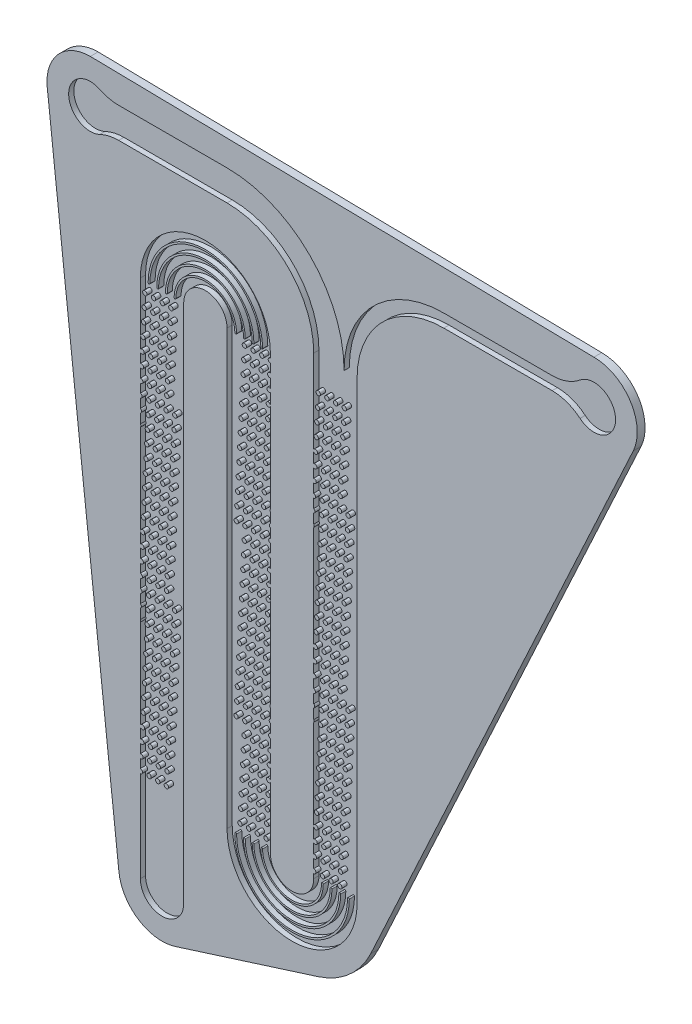
SolidWorks part; units mm, degrees
ref_plane "Front Plane" through (0, 0, 0) normal (0, 0, 1) x (1, 0, 0)
ref_plane "Top Plane" through (0, 0, 0) normal (0, 1, 0) x (1, 0, 0)
ref_plane "Right Plane" through (0, 0, 0) normal (1, 0, 0) x (0, 0, -1)
sketch "Model" plane through (0, 0, 0) normal (0, 0, 1) x (1, 0, 0)
  line L0 (0, 0) -> (0, 1)
  line L1 (0, 2) -> (0, 4.0254)
  line L2 (0, 4.9746) -> (0, 7.1113)
  line L3 (0, 7.8887) -> (0, 10.3341)
  line L4 (0, 10.6659) -> (0, 31.2411)
  line L5 (0, 31.7589) -> (0, 34.0795)
  line L6 (0, 34.9205) -> (0, 37.013)
  line L7 (0, 37.987) -> (0, 40.0019)
  line L8 (0, 40.9981) -> (0, 43.0422)
  line L9 (0, 43.9578) -> (0, 46.1513)
  line L10 (0, 46.8487) -> (0, 70.1796)
  line L11 (0, 70.8204) -> (0, 73.0543)
  line L12 (0, 73.9457) -> (0, 76.0048)
  line L13 (0, 76.9952) -> (0, 79.0078)
  line L14 (0, 79.9922) -> (0, 82.0642)
  line L15 (0, 82.9358) -> (0, 85.203)
  line L16 (0, 85.797) -> (0, 100)
  line L17 (10, 0) -> (10, 100)
  line L18 (30, 100) -> (30, 99)
  line L19 (30, 98) -> (30, 95.9746)
  line L20 (30, 95.0254) -> (30, 92.8887)
  line L21 (30, 92.1113) -> (30, 89.6659)
  line L22 (30, 89.3341) -> (30, 68.7589)
  line L23 (30, 68.2411) -> (30, 65.9205)
  line L24 (30, 65.0795) -> (30, 62.987)
  line L25 (30, 62.013) -> (30, 59.9981)
  line L26 (30, 59.0019) -> (30, 56.9578)
  line L27 (30, 56.0422) -> (30, 53.8487)
  line L28 (30, 53.1513) -> (30, 29.8204)
  line L29 (30, 29.1796) -> (30, 26.9457)
  line L30 (30, 26.0543) -> (30, 23.9952)
  line L31 (30, 23.0048) -> (30, 20.9922)
  line L32 (30, 20.0078) -> (30, 17.9358)
  line L33 (30, 17.0642) -> (30, 14.797)
  line L34 (30, 14.203) -> (30, 0)
  line L35 (20, 100) -> (20, 0)
  line L36 (40, 0) -> (40, 1)
  line L37 (40, 2) -> (40, 4.0254)
  line L38 (40, 4.9746) -> (40, 7.1113)
  line L39 (40, 7.8887) -> (40, 10.3341)
  line L40 (40, 10.6659) -> (40, 31.2411)
  line L41 (40, 31.7589) -> (40, 34.0795)
  line L42 (40, 34.9205) -> (40, 37.013)
  line L43 (40, 37.987) -> (40, 40.0019)
  line L44 (40, 40.9981) -> (40, 43.0422)
  line L45 (40, 43.9578) -> (40, 46.1513)
  line L46 (40, 46.8487) -> (40, 70.1796)
  line L47 (40, 70.8204) -> (40, 73.0543)
  line L48 (40, 73.9457) -> (40, 76.0048)
  line L49 (40, 76.9952) -> (40, 79.0078)
  line L50 (40, 79.9922) -> (40, 82.0642)
  line L51 (40, 82.9358) -> (40, 85.203)
  line L52 (40, 85.797) -> (40, 100)
  line L53 (50, 0) -> (50, 100)
  line L54 (0, 0) -> (0, -20)
  line L55 (10, 0) -> (10, -20)
  line L56 (75, 125) -> (95, 125)
  line L57 (75, 128) -> (95, 128)
  line L58 (75, 125) -> (70, 125)
  line L59 (75, 128) -> (70, 128)
  line L60 (15, 125) -> (-5, 125)
  line L61 (15, 132) -> (-5, 132)
  line L62 (15, 125) -> (20, 125)
  line L63 (15, 132) -> (20, 132)
  line L64 (40, 100) -> (40, 105)
  line L65 (50, 100) -> (50, 105)
  arc A0 (0, 1) -> (0, 2) centre (0, 1.5) ccw
  circle A1 centre (2, 1.5) radius 0.5
  circle A2 centre (4, 1.5) radius 0.5
  circle A3 centre (6, 1.5) radius 0.5
  arc A4 (0, 4.0254) -> (0, 4.9746) centre (0.1572, 4.5) ccw
  circle A5 centre (2.1572, 4.5) radius 0.5
  circle A6 centre (4.1572, 4.5) radius 0.5
  circle A7 centre (6.1572, 4.5) radius 0.5
  arc A8 (0, 7.1113) -> (0, 7.8887) centre (0.3144, 7.5) ccw
  circle A9 centre (2.3144, 7.5) radius 0.5
  circle A10 centre (4.3144, 7.5) radius 0.5
  circle A11 centre (6.3144, 7.5) radius 0.5
  arc A12 (0, 10.3341) -> (0, 10.6659) centre (0.4717, 10.5) ccw
  circle A13 centre (2.4717, 10.5) radius 0.5
  circle A14 centre (4.4717, 10.5) radius 0.5
  circle A15 centre (6.4717, 10.5) radius 0.5
  circle A16 centre (0.6289, 13.5) radius 0.5
  circle A17 centre (2.6289, 13.5) radius 0.5
  circle A18 centre (4.6289, 13.5) radius 0.5
  circle A19 centre (6.6289, 13.5) radius 0.5
  circle A20 centre (0.7861, 16.5) radius 0.5
  circle A21 centre (2.7861, 16.5) radius 0.5
  circle A22 centre (4.7861, 16.5) radius 0.5
  circle A23 centre (6.7861, 16.5) radius 0.5
  circle A24 centre (0.9433, 19.5) radius 0.5
  circle A25 centre (2.9433, 19.5) radius 0.5
  circle A26 centre (4.9433, 19.5) radius 0.5
  circle A27 centre (6.9433, 19.5) radius 0.5
  circle A28 centre (1.1006, 22.5) radius 0.5
  circle A29 centre (3.1006, 22.5) radius 0.5
  circle A30 centre (5.1006, 22.5) radius 0.5
  circle A31 centre (7.1006, 22.5) radius 0.5
  circle A32 centre (1.2578, 25.5) radius 0.5
  circle A33 centre (3.2578, 25.5) radius 0.5
  circle A34 centre (5.2578, 25.5) radius 0.5
  circle A35 centre (7.2578, 25.5) radius 0.5
  circle A36 centre (1.415, 28.5) radius 0.5
  circle A37 centre (3.415, 28.5) radius 0.5
  circle A38 centre (5.415, 28.5) radius 0.5
  circle A39 centre (7.415, 28.5) radius 0.5
  arc A40 (0, 31.2411) -> (0, 31.7589) centre (-0.4278, 31.5) ccw
  circle A41 centre (1.5722, 31.5) radius 0.5
  circle A42 centre (3.5722, 31.5) radius 0.5
  circle A43 centre (5.5722, 31.5) radius 0.5
  circle A44 centre (7.5722, 31.5) radius 0.5
  arc A45 (0, 34.0795) -> (0, 34.9205) centre (-0.2705, 34.5) ccw
  circle A46 centre (1.7295, 34.5) radius 0.5
  circle A47 centre (3.7295, 34.5) radius 0.5
  circle A48 centre (5.7295, 34.5) radius 0.5
  circle A49 centre (7.7295, 34.5) radius 0.5
  arc A50 (0, 37.013) -> (0, 37.987) centre (-0.1133, 37.5) ccw
  circle A51 centre (1.8867, 37.5) radius 0.5
  circle A52 centre (3.8867, 37.5) radius 0.5
  circle A53 centre (5.8867, 37.5) radius 0.5
  circle A54 centre (7.8867, 37.5) radius 0.5
  arc A55 (0, 40.0019) -> (0, 40.9981) centre (0, 40.5) ccw
  circle A56 centre (2.0439, 40.5) radius 0.5
  circle A57 centre (4.0439, 40.5) radius 0.5
  circle A58 centre (6.0439, 40.5) radius 0.5
  arc A59 (0, 43.0422) -> (0, 43.9578) centre (0.2011, 43.5) ccw
  circle A60 centre (2.2011, 43.5) radius 0.5
  circle A61 centre (4.2011, 43.5) radius 0.5
  circle A62 centre (6.2011, 43.5) radius 0.5
  arc A63 (0, 46.1513) -> (0, 46.8487) centre (0.3584, 46.5) ccw
  circle A64 centre (2.3584, 46.5) radius 0.5
  circle A65 centre (4.3584, 46.5) radius 0.5
  circle A66 centre (6.3584, 46.5) radius 0.5
  circle A67 centre (0.5156, 49.5) radius 0.5
  circle A68 centre (2.5156, 49.5) radius 0.5
  circle A69 centre (4.5156, 49.5) radius 0.5
  circle A70 centre (6.5156, 49.5) radius 0.5
  circle A71 centre (0.6728, 52.5) radius 0.5
  circle A72 centre (2.6728, 52.5) radius 0.5
  circle A73 centre (4.6728, 52.5) radius 0.5
  circle A74 centre (6.6728, 52.5) radius 0.5
  circle A75 centre (0.83, 55.5) radius 0.5
  circle A76 centre (2.83, 55.5) radius 0.5
  circle A77 centre (4.83, 55.5) radius 0.5
  circle A78 centre (6.83, 55.5) radius 0.5
  circle A79 centre (0.9872, 58.5) radius 0.5
  circle A80 centre (2.9872, 58.5) radius 0.5
  circle A81 centre (4.9872, 58.5) radius 0.5
  circle A82 centre (6.9872, 58.5) radius 0.5
  circle A83 centre (1.1445, 61.5) radius 0.5
  circle A84 centre (3.1445, 61.5) radius 0.5
  circle A85 centre (5.1445, 61.5) radius 0.5
  circle A86 centre (7.1445, 61.5) radius 0.5
  circle A87 centre (1.3017, 64.5) radius 0.5
  circle A88 centre (3.3017, 64.5) radius 0.5
  circle A89 centre (5.3017, 64.5) radius 0.5
  circle A90 centre (7.3017, 64.5) radius 0.5
  circle A91 centre (1.4589, 67.5) radius 0.5
  circle A92 centre (3.4589, 67.5) radius 0.5
  circle A93 centre (5.4589, 67.5) radius 0.5
  circle A94 centre (7.4589, 67.5) radius 0.5
  arc A95 (0, 70.1796) -> (0, 70.8204) centre (-0.3839, 70.5) ccw
  circle A96 centre (1.6161, 70.5) radius 0.5
  circle A97 centre (3.6161, 70.5) radius 0.5
  circle A98 centre (5.6161, 70.5) radius 0.5
  circle A99 centre (7.6161, 70.5) radius 0.5
  arc A100 (0, 73.0543) -> (0, 73.9457) centre (-0.2266, 73.5) ccw
  circle A101 centre (1.7734, 73.5) radius 0.5
  circle A102 centre (3.7734, 73.5) radius 0.5
  circle A103 centre (5.7734, 73.5) radius 0.5
  circle A104 centre (7.7734, 73.5) radius 0.5
  arc A105 (0, 76.0048) -> (0, 76.9952) centre (-0.0694, 76.5) ccw
  circle A106 centre (1.9306, 76.5) radius 0.5
  circle A107 centre (3.9306, 76.5) radius 0.5
  circle A108 centre (5.9306, 76.5) radius 0.5
  circle A109 centre (7.9306, 76.5) radius 0.5
  arc A110 (0, 79.0078) -> (0, 79.9922) centre (0.0878, 79.5) ccw
  circle A111 centre (2.0878, 79.5) radius 0.5
  circle A112 centre (4.0878, 79.5) radius 0.5
  circle A113 centre (6.0878, 79.5) radius 0.5
  arc A114 (0, 82.0642) -> (0, 82.9358) centre (0.245, 82.5) ccw
  circle A115 centre (2.245, 82.5) radius 0.5
  circle A116 centre (4.245, 82.5) radius 0.5
  circle A117 centre (6.245, 82.5) radius 0.5
  arc A118 (0, 85.203) -> (0, 85.797) centre (0.4023, 85.5) ccw
  circle A119 centre (2.4023, 85.5) radius 0.5
  circle A120 centre (4.4023, 85.5) radius 0.5
  circle A121 centre (6.4023, 85.5) radius 0.5
  circle A122 centre (0.5595, 88.5) radius 0.5
  circle A123 centre (2.5595, 88.5) radius 0.5
  circle A124 centre (4.5595, 88.5) radius 0.5
  circle A125 centre (6.5595, 88.5) radius 0.5
  circle A126 centre (0.7167, 91.5) radius 0.5
  circle A127 centre (2.7167, 91.5) radius 0.5
  circle A128 centre (4.7167, 91.5) radius 0.5
  circle A129 centre (6.7167, 91.5) radius 0.5
  circle A130 centre (0.8739, 94.5) radius 0.5
  circle A131 centre (2.8739, 94.5) radius 0.5
  circle A132 centre (4.8739, 94.5) radius 0.5
  circle A133 centre (6.8739, 94.5) radius 0.5
  circle A134 centre (1.0311, 97.5) radius 0.5
  circle A135 centre (3.0311, 97.5) radius 0.5
  circle A136 centre (5.0311, 97.5) radius 0.5
  circle A137 centre (7.0311, 97.5) radius 0.5
  arc A138 (20, 100) -> (10, 100) centre (15, 100) ccw
  arc A139 (30, 100) -> (0, 100) centre (15, 100) ccw
  arc A140 (22.2, 100) -> (7.8, 100) centre (15, 100) ccw
  arc A141 (24.2, 100) -> (5.8, 100) centre (15, 100) ccw
  arc A142 (26.2, 100) -> (3.8, 100) centre (15, 100) ccw
  arc A143 (28.2, 100) -> (1.8, 100) centre (15, 100) ccw
  arc A144 (21.8, 100) -> (8.2, 100) centre (15, 100) ccw
  arc A145 (23.8, 100) -> (6.2, 100) centre (15, 100) ccw
  arc A146 (25.8, 100) -> (4.2, 100) centre (15, 100) ccw
  arc A147 (27.8, 100) -> (2.2, 100) centre (15, 100) ccw
  arc A148 (21.8, 100) -> (22.2, 100) centre (22, 100) ccw
  arc A149 (7.8, 100) -> (8.2, 100) centre (8, 100) ccw
  arc A150 (23.8, 100) -> (24.2, 100) centre (24, 100) ccw
  arc A151 (5.8, 100) -> (6.2, 100) centre (6, 100) ccw
  arc A152 (25.8, 100) -> (26.2, 100) centre (26, 100) ccw
  arc A153 (3.8, 100) -> (4.2, 100) centre (4, 100) ccw
  arc A154 (27.8, 100) -> (28.2, 100) centre (28, 100) ccw
  arc A155 (1.8, 100) -> (2.2, 100) centre (2, 100) ccw
  arc A156 (30, 0) -> (40, 0) centre (35, 0) ccw
  arc A157 (20, 0) -> (50, 0) centre (35, 0) ccw
  arc A158 (27.8, 0) -> (42.2, 0) centre (35, 0) ccw
  arc A159 (25.8, 0) -> (44.2, 0) centre (35, 0) ccw
  arc A160 (23.8, 0) -> (46.2, 0) centre (35, 0) ccw
  arc A161 (21.8, 0) -> (48.2, 0) centre (35, 0) ccw
  arc A162 (28.2, 0) -> (41.8, 0) centre (35, 0) ccw
  arc A163 (26.2, 0) -> (43.8, 0) centre (35, 0) ccw
  arc A164 (24.2, 0) -> (45.8, 0) centre (35, 0) ccw
  arc A165 (22.2, 0) -> (47.8, 0) centre (35, 0) ccw
  arc A166 (42.2, 0) -> (41.8, 0) centre (42, 0) ccw
  arc A167 (28.2, 0) -> (27.8, 0) centre (28, 0) ccw
  arc A168 (44.2, 0) -> (43.8, 0) centre (44, 0) ccw
  arc A169 (26.2, 0) -> (25.8, 0) centre (26, 0) ccw
  arc A170 (46.2, 0) -> (45.8, 0) centre (46, 0) ccw
  arc A171 (24.2, 0) -> (23.8, 0) centre (24, 0) ccw
  arc A172 (48.2, 0) -> (47.8, 0) centre (48, 0) ccw
  arc A173 (22.2, 0) -> (21.8, 0) centre (22, 0) ccw
  arc A174 (30, 99) -> (30, 98) centre (30, 98.5) ccw
  circle A175 centre (28, 98.5) radius 0.5
  circle A176 centre (26, 98.5) radius 0.5
  circle A177 centre (24, 98.5) radius 0.5
  arc A178 (30, 95.9746) -> (30, 95.0254) centre (29.8428, 95.5) ccw
  circle A179 centre (27.8428, 95.5) radius 0.5
  circle A180 centre (25.8428, 95.5) radius 0.5
  circle A181 centre (23.8428, 95.5) radius 0.5
  arc A182 (30, 92.8887) -> (30, 92.1113) centre (29.6856, 92.5) ccw
  circle A183 centre (27.6856, 92.5) radius 0.5
  circle A184 centre (25.6856, 92.5) radius 0.5
  circle A185 centre (23.6856, 92.5) radius 0.5
  arc A186 (30, 89.6659) -> (30, 89.3341) centre (29.5283, 89.5) ccw
  circle A187 centre (27.5283, 89.5) radius 0.5
  circle A188 centre (25.5283, 89.5) radius 0.5
  circle A189 centre (23.5283, 89.5) radius 0.5
  circle A190 centre (29.3711, 86.5) radius 0.5
  circle A191 centre (27.3711, 86.5) radius 0.5
  circle A192 centre (25.3711, 86.5) radius 0.5
  circle A193 centre (23.3711, 86.5) radius 0.5
  circle A194 centre (29.2139, 83.5) radius 0.5
  circle A195 centre (27.2139, 83.5) radius 0.5
  circle A196 centre (25.2139, 83.5) radius 0.5
  circle A197 centre (23.2139, 83.5) radius 0.5
  circle A198 centre (29.0567, 80.5) radius 0.5
  circle A199 centre (27.0567, 80.5) radius 0.5
  circle A200 centre (25.0567, 80.5) radius 0.5
  circle A201 centre (23.0567, 80.5) radius 0.5
  circle A202 centre (28.8994, 77.5) radius 0.5
  circle A203 centre (26.8994, 77.5) radius 0.5
  circle A204 centre (24.8994, 77.5) radius 0.5
  circle A205 centre (22.8994, 77.5) radius 0.5
  circle A206 centre (28.7422, 74.5) radius 0.5
  circle A207 centre (26.7422, 74.5) radius 0.5
  circle A208 centre (24.7422, 74.5) radius 0.5
  circle A209 centre (22.7422, 74.5) radius 0.5
  circle A210 centre (28.585, 71.5) radius 0.5
  circle A211 centre (26.585, 71.5) radius 0.5
  circle A212 centre (24.585, 71.5) radius 0.5
  circle A213 centre (22.585, 71.5) radius 0.5
  arc A214 (30, 68.7589) -> (30, 68.2411) centre (30.4278, 68.5) ccw
  circle A215 centre (28.4278, 68.5) radius 0.5
  circle A216 centre (26.4278, 68.5) radius 0.5
  circle A217 centre (24.4278, 68.5) radius 0.5
  circle A218 centre (22.4278, 68.5) radius 0.5
  arc A219 (30, 65.9205) -> (30, 65.0795) centre (30.2705, 65.5) ccw
  circle A220 centre (28.2705, 65.5) radius 0.5
  circle A221 centre (26.2705, 65.5) radius 0.5
  circle A222 centre (24.2705, 65.5) radius 0.5
  circle A223 centre (22.2705, 65.5) radius 0.5
  arc A224 (30, 62.987) -> (30, 62.013) centre (30.1133, 62.5) ccw
  circle A225 centre (28.1133, 62.5) radius 0.5
  circle A226 centre (26.1133, 62.5) radius 0.5
  circle A227 centre (24.1133, 62.5) radius 0.5
  circle A228 centre (22.1133, 62.5) radius 0.5
  arc A229 (30, 59.9981) -> (30, 59.0019) centre (29.9561, 59.5) ccw
  circle A230 centre (27.9561, 59.5) radius 0.5
  circle A231 centre (25.9561, 59.5) radius 0.5
  circle A232 centre (23.9561, 59.5) radius 0.5
  arc A233 (30, 56.9578) -> (30, 56.0422) centre (29.7989, 56.5) ccw
  circle A234 centre (27.7989, 56.5) radius 0.5
  circle A235 centre (25.7989, 56.5) radius 0.5
  circle A236 centre (23.7989, 56.5) radius 0.5
  arc A237 (30, 53.8487) -> (30, 53.1513) centre (29.6416, 53.5) ccw
  circle A238 centre (27.6416, 53.5) radius 0.5
  circle A239 centre (25.6416, 53.5) radius 0.5
  circle A240 centre (23.6416, 53.5) radius 0.5
  circle A241 centre (29.4844, 50.5) radius 0.5
  circle A242 centre (27.4844, 50.5) radius 0.5
  circle A243 centre (25.4844, 50.5) radius 0.5
  circle A244 centre (23.4844, 50.5) radius 0.5
  circle A245 centre (29.3272, 47.5) radius 0.5
  circle A246 centre (27.3272, 47.5) radius 0.5
  circle A247 centre (25.3272, 47.5) radius 0.5
  circle A248 centre (23.3272, 47.5) radius 0.5
  circle A249 centre (29.17, 44.5) radius 0.5
  circle A250 centre (27.17, 44.5) radius 0.5
  circle A251 centre (25.17, 44.5) radius 0.5
  circle A252 centre (23.17, 44.5) radius 0.5
  circle A253 centre (29.0128, 41.5) radius 0.5
  circle A254 centre (27.0128, 41.5) radius 0.5
  circle A255 centre (25.0128, 41.5) radius 0.5
  circle A256 centre (23.0128, 41.5) radius 0.5
  circle A257 centre (28.8555, 38.5) radius 0.5
  circle A258 centre (26.8555, 38.5) radius 0.5
  circle A259 centre (24.8555, 38.5) radius 0.5
  circle A260 centre (22.8555, 38.5) radius 0.5
  circle A261 centre (28.6983, 35.5) radius 0.5
  circle A262 centre (26.6983, 35.5) radius 0.5
  circle A263 centre (24.6983, 35.5) radius 0.5
  circle A264 centre (22.6983, 35.5) radius 0.5
  circle A265 centre (28.5411, 32.5) radius 0.5
  circle A266 centre (26.5411, 32.5) radius 0.5
  circle A267 centre (24.5411, 32.5) radius 0.5
  circle A268 centre (22.5411, 32.5) radius 0.5
  arc A269 (30, 29.8204) -> (30, 29.1796) centre (30.3839, 29.5) ccw
  circle A270 centre (28.3839, 29.5) radius 0.5
  circle A271 centre (26.3839, 29.5) radius 0.5
  circle A272 centre (24.3839, 29.5) radius 0.5
  circle A273 centre (22.3839, 29.5) radius 0.5
  arc A274 (30, 26.9457) -> (30, 26.0543) centre (30.2266, 26.5) ccw
  circle A275 centre (28.2266, 26.5) radius 0.5
  circle A276 centre (26.2266, 26.5) radius 0.5
  circle A277 centre (24.2266, 26.5) radius 0.5
  circle A278 centre (22.2266, 26.5) radius 0.5
  arc A279 (30, 23.9952) -> (30, 23.0048) centre (30.0694, 23.5) ccw
  circle A280 centre (28.0694, 23.5) radius 0.5
  circle A281 centre (26.0694, 23.5) radius 0.5
  circle A282 centre (24.0694, 23.5) radius 0.5
  circle A283 centre (22.0694, 23.5) radius 0.5
  arc A284 (30, 20.9922) -> (30, 20.0078) centre (29.9122, 20.5) ccw
  circle A285 centre (27.9122, 20.5) radius 0.5
  circle A286 centre (25.9122, 20.5) radius 0.5
  circle A287 centre (23.9122, 20.5) radius 0.5
  arc A288 (30, 17.9358) -> (30, 17.0642) centre (29.755, 17.5) ccw
  circle A289 centre (27.755, 17.5) radius 0.5
  circle A290 centre (25.755, 17.5) radius 0.5
  circle A291 centre (23.755, 17.5) radius 0.5
  arc A292 (30, 14.797) -> (30, 14.203) centre (29.5977, 14.5) ccw
  circle A293 centre (27.5977, 14.5) radius 0.5
  circle A294 centre (25.5977, 14.5) radius 0.5
  circle A295 centre (23.5977, 14.5) radius 0.5
  circle A296 centre (29.4405, 11.5) radius 0.5
  circle A297 centre (27.4405, 11.5) radius 0.5
  circle A298 centre (25.4405, 11.5) radius 0.5
  circle A299 centre (23.4405, 11.5) radius 0.5
  circle A300 centre (29.2833, 8.5) radius 0.5
  circle A301 centre (27.2833, 8.5) radius 0.5
  circle A302 centre (25.2833, 8.5) radius 0.5
  circle A303 centre (23.2833, 8.5) radius 0.5
  circle A304 centre (29.1261, 5.5) radius 0.5
  circle A305 centre (27.1261, 5.5) radius 0.5
  circle A306 centre (25.1261, 5.5) radius 0.5
  circle A307 centre (23.1261, 5.5) radius 0.5
  circle A308 centre (28.9689, 2.5) radius 0.5
  circle A309 centre (26.9689, 2.5) radius 0.5
  circle A310 centre (24.9689, 2.5) radius 0.5
  circle A311 centre (22.9689, 2.5) radius 0.5
  arc A312 (40, 1) -> (40, 2) centre (40, 1.5) ccw
  circle A313 centre (42, 1.5) radius 0.5
  circle A314 centre (44, 1.5) radius 0.5
  circle A315 centre (46, 1.5) radius 0.5
  arc A316 (40, 4.0254) -> (40, 4.9746) centre (40.1572, 4.5) ccw
  circle A317 centre (42.1572, 4.5) radius 0.5
  circle A318 centre (44.1572, 4.5) radius 0.5
  circle A319 centre (46.1572, 4.5) radius 0.5
  arc A320 (40, 7.1113) -> (40, 7.8887) centre (40.3144, 7.5) ccw
  circle A321 centre (42.3144, 7.5) radius 0.5
  circle A322 centre (44.3144, 7.5) radius 0.5
  circle A323 centre (46.3144, 7.5) radius 0.5
  arc A324 (40, 10.3341) -> (40, 10.6659) centre (40.4717, 10.5) ccw
  circle A325 centre (42.4717, 10.5) radius 0.5
  circle A326 centre (44.4717, 10.5) radius 0.5
  circle A327 centre (46.4717, 10.5) radius 0.5
  circle A328 centre (40.6289, 13.5) radius 0.5
  circle A329 centre (42.6289, 13.5) radius 0.5
  circle A330 centre (44.6289, 13.5) radius 0.5
  circle A331 centre (46.6289, 13.5) radius 0.5
  circle A332 centre (40.7861, 16.5) radius 0.5
  circle A333 centre (42.7861, 16.5) radius 0.5
  circle A334 centre (44.7861, 16.5) radius 0.5
  circle A335 centre (46.7861, 16.5) radius 0.5
  circle A336 centre (40.9433, 19.5) radius 0.5
  circle A337 centre (42.9433, 19.5) radius 0.5
  circle A338 centre (44.9433, 19.5) radius 0.5
  circle A339 centre (46.9433, 19.5) radius 0.5
  circle A340 centre (41.1006, 22.5) radius 0.5
  circle A341 centre (43.1006, 22.5) radius 0.5
  circle A342 centre (45.1006, 22.5) radius 0.5
  circle A343 centre (47.1006, 22.5) radius 0.5
  circle A344 centre (41.2578, 25.5) radius 0.5
  circle A345 centre (43.2578, 25.5) radius 0.5
  circle A346 centre (45.2578, 25.5) radius 0.5
  circle A347 centre (47.2578, 25.5) radius 0.5
  circle A348 centre (41.415, 28.5) radius 0.5
  circle A349 centre (43.415, 28.5) radius 0.5
  circle A350 centre (45.415, 28.5) radius 0.5
  circle A351 centre (47.415, 28.5) radius 0.5
  arc A352 (40, 31.2411) -> (40, 31.7589) centre (39.5722, 31.5) ccw
  circle A353 centre (41.5722, 31.5) radius 0.5
  circle A354 centre (43.5722, 31.5) radius 0.5
  circle A355 centre (45.5722, 31.5) radius 0.5
  circle A356 centre (47.5722, 31.5) radius 0.5
  arc A357 (40, 34.0795) -> (40, 34.9205) centre (39.7295, 34.5) ccw
  circle A358 centre (41.7295, 34.5) radius 0.5
  circle A359 centre (43.7295, 34.5) radius 0.5
  circle A360 centre (45.7295, 34.5) radius 0.5
  circle A361 centre (47.7295, 34.5) radius 0.5
  arc A362 (40, 37.013) -> (40, 37.987) centre (39.8867, 37.5) ccw
  circle A363 centre (41.8867, 37.5) radius 0.5
  circle A364 centre (43.8867, 37.5) radius 0.5
  circle A365 centre (45.8867, 37.5) radius 0.5
  circle A366 centre (47.8867, 37.5) radius 0.5
  arc A367 (40, 40.0019) -> (40, 40.9981) centre (40.0439, 40.5) ccw
  circle A368 centre (42.0439, 40.5) radius 0.5
  circle A369 centre (44.0439, 40.5) radius 0.5
  circle A370 centre (46.0439, 40.5) radius 0.5
  arc A371 (40, 43.0422) -> (40, 43.9578) centre (40.2011, 43.5) ccw
  circle A372 centre (42.2011, 43.5) radius 0.5
  circle A373 centre (44.2011, 43.5) radius 0.5
  circle A374 centre (46.2011, 43.5) radius 0.5
  arc A375 (40, 46.1513) -> (40, 46.8487) centre (40.3584, 46.5) ccw
  circle A376 centre (42.3584, 46.5) radius 0.5
  circle A377 centre (44.3584, 46.5) radius 0.5
  circle A378 centre (46.3584, 46.5) radius 0.5
  circle A379 centre (40.5156, 49.5) radius 0.5
  circle A380 centre (42.5156, 49.5) radius 0.5
  circle A381 centre (44.5156, 49.5) radius 0.5
  circle A382 centre (46.5156, 49.5) radius 0.5
  circle A383 centre (40.6728, 52.5) radius 0.5
  circle A384 centre (42.6728, 52.5) radius 0.5
  circle A385 centre (44.6728, 52.5) radius 0.5
  circle A386 centre (46.6728, 52.5) radius 0.5
  circle A387 centre (40.83, 55.5) radius 0.5
  circle A388 centre (42.83, 55.5) radius 0.5
  circle A389 centre (44.83, 55.5) radius 0.5
  circle A390 centre (46.83, 55.5) radius 0.5
  circle A391 centre (40.9872, 58.5) radius 0.5
  circle A392 centre (42.9872, 58.5) radius 0.5
  circle A393 centre (44.9872, 58.5) radius 0.5
  circle A394 centre (46.9872, 58.5) radius 0.5
  circle A395 centre (41.1445, 61.5) radius 0.5
  circle A396 centre (43.1445, 61.5) radius 0.5
  circle A397 centre (45.1445, 61.5) radius 0.5
  circle A398 centre (47.1445, 61.5) radius 0.5
  circle A399 centre (41.3017, 64.5) radius 0.5
  circle A400 centre (43.3017, 64.5) radius 0.5
  circle A401 centre (45.3017, 64.5) radius 0.5
  circle A402 centre (47.3017, 64.5) radius 0.5
  circle A403 centre (41.4589, 67.5) radius 0.5
  circle A404 centre (43.4589, 67.5) radius 0.5
  circle A405 centre (45.4589, 67.5) radius 0.5
  circle A406 centre (47.4589, 67.5) radius 0.5
  arc A407 (40, 70.1796) -> (40, 70.8204) centre (39.6161, 70.5) ccw
  circle A408 centre (41.6161, 70.5) radius 0.5
  circle A409 centre (43.6161, 70.5) radius 0.5
  circle A410 centre (45.6161, 70.5) radius 0.5
  circle A411 centre (47.6161, 70.5) radius 0.5
  arc A412 (40, 73.0543) -> (40, 73.9457) centre (39.7734, 73.5) ccw
  circle A413 centre (41.7734, 73.5) radius 0.5
  circle A414 centre (43.7734, 73.5) radius 0.5
  circle A415 centre (45.7734, 73.5) radius 0.5
  circle A416 centre (47.7734, 73.5) radius 0.5
  arc A417 (40, 76.0048) -> (40, 76.9952) centre (39.9306, 76.5) ccw
  circle A418 centre (41.9306, 76.5) radius 0.5
  circle A419 centre (43.9306, 76.5) radius 0.5
  circle A420 centre (45.9306, 76.5) radius 0.5
  circle A421 centre (47.9306, 76.5) radius 0.5
  arc A422 (40, 79.0078) -> (40, 79.9922) centre (40.0878, 79.5) ccw
  circle A423 centre (42.0878, 79.5) radius 0.5
  circle A424 centre (44.0878, 79.5) radius 0.5
  circle A425 centre (46.0878, 79.5) radius 0.5
  arc A426 (40, 82.0642) -> (40, 82.9358) centre (40.245, 82.5) ccw
  circle A427 centre (42.245, 82.5) radius 0.5
  circle A428 centre (44.245, 82.5) radius 0.5
  circle A429 centre (46.245, 82.5) radius 0.5
  arc A430 (40, 85.203) -> (40, 85.797) centre (40.4023, 85.5) ccw
  circle A431 centre (42.4023, 85.5) radius 0.5
  circle A432 centre (44.4023, 85.5) radius 0.5
  circle A433 centre (46.4023, 85.5) radius 0.5
  circle A434 centre (40.5595, 88.5) radius 0.5
  circle A435 centre (42.5595, 88.5) radius 0.5
  circle A436 centre (44.5595, 88.5) radius 0.5
  circle A437 centre (46.5595, 88.5) radius 0.5
  circle A438 centre (40.7167, 91.5) radius 0.5
  circle A439 centre (42.7167, 91.5) radius 0.5
  circle A440 centre (44.7167, 91.5) radius 0.5
  circle A441 centre (46.7167, 91.5) radius 0.5
  circle A442 centre (40.8739, 94.5) radius 0.5
  circle A443 centre (42.8739, 94.5) radius 0.5
  circle A444 centre (44.8739, 94.5) radius 0.5
  circle A445 centre (46.8739, 94.5) radius 0.5
  circle A446 centre (41.0311, 97.5) radius 0.5
  circle A447 centre (43.0311, 97.5) radius 0.5
  circle A448 centre (45.0311, 97.5) radius 0.5
  circle A449 centre (47.0311, 97.5) radius 0.5
  arc A450 (0, -20) -> (10, -20) centre (5, -20) ccw
  arc A453 (101.4205, 122.6667) -> (101.4205, 130.3333) centre (104.6307, 126.5) ccw
  arc A454 (101.4205, 122.6667) -> (95, 125) centre (95, 115) ccw
  arc A455 (95, 128) -> (101.4205, 130.3333) centre (95, 138) ccw
  arc A456 (70, 125) -> (50, 105) centre (70, 105) ccw
  arc A457 (70, 128) -> (47, 105) centre (70, 105) ccw
  arc A458 (-9.3589, 133) -> (-9.3589, 124) centre (-11.5383, 128.5) ccw
  arc A459 (-5, 125) -> (-9.3589, 124) centre (-5, 115) ccw
  arc A460 (-9.3589, 133) -> (-5, 132) centre (-5, 142) ccw
  arc A461 (40, 105) -> (20, 125) centre (20, 105) ccw
  arc A462 (47, 105) -> (20, 132) centre (20, 105) ccw
extrude "Boss-Extrude1" add sketch "Model" along normal blind 1.2
sketch "Sketch2" plane through (0, 0, 0) normal (0, 0, 1) x (1, 0, 0)
  line L0 (-21.4769, 127.3931) -> (-4.9386, -21.1069)
  line L1 (8.0217, -29.5325) -> (41.0434, -19.0651)
  line L2 (113.7041, 122.2961) -> (53.1469, -8.4078)
  line L3 (104.6307, 136.5) -> (-11.5383, 138.5)
  arc A0 (-11.1941, 138.4941) -> (-21.4769, 127.3931) centre (-11.5383, 128.5) ccw
  arc A1 (113.7041, 122.2961) -> (104.6307, 136.5) centre (104.6307, 126.5) ccw
  arc A2 (-4.9386, -21.1069) -> (8.0217, -29.5325) centre (5, -20) ccw
  arc A3 (41.0434, -19.0651) -> (53.1469, -8.4078) centre (35, 0) ccw
  dimension "D1" = 20
  dimension "D2" = 40
extrude "Boss-Extrude2" add sketch "Sketch2" along normal up to surface (1.2 mm away) and the other way blind 0.6 separate body contours L1 A3 L2 A1 L3 A0 L0 A2 region at (36.4708, 69.1316, 0) up to face at (45.5311, 97.5, 1.2)
combine bodies "Combine1" operation type subtract main body 102 bodies to subtract 101
